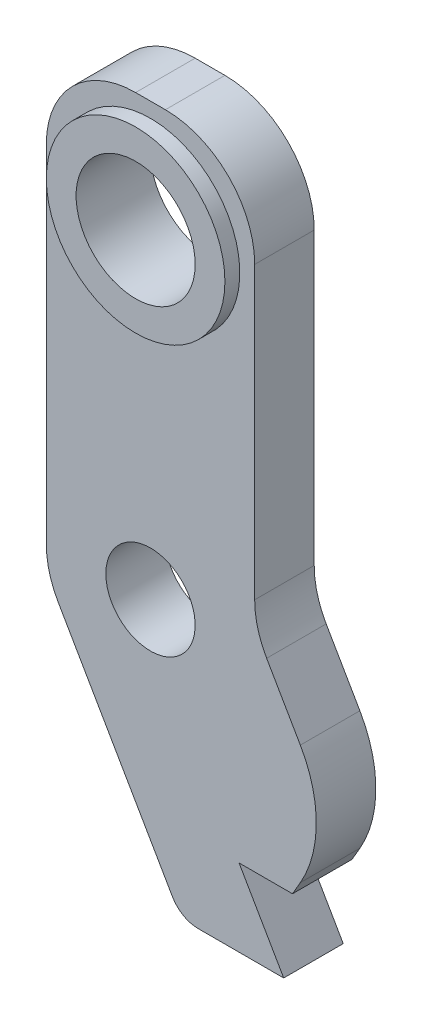
SolidWorks part; units mm, degrees
ref_plane "前视基准面" through (0, 0, 0) normal (0, 0, 1) x (1, 0, 0)
ref_plane "上视基准面" through (0, 0, 0) normal (0, 1, 0) x (1, 0, 0)
ref_plane "右视基准面" through (0, 0, 0) normal (1, 0, 0) x (0, 0, -1)
sketch "草图1" plane through (0, 0, -37.2525) normal (0, 0, 1) x (1, 0, 0)
  line L0 (-5.7048, 8.9994) -> (-14.0004, 8.9994) construction
  line L1 (-14.0004, 8.9994) -> (-11.3913, 4.4807) construction
  line L2 (-14.0004, 8.9994) -> (-14.0004, 23.4994) construction
  line L3 (-10.5004, 9.9373) -> (-10.5004, 23.4994)
  line L5 (-10.5004, 23.4994) -> (-17.5004, 23.4994)
  line L6 (-17.5004, 8.0615) -> (-12.976, 0.2258)
  line L7 (-17.5004, 23.4994) -> (-17.5004, 8.0615)
  line L11 (-12.976, 0.2258) -> (-9.5249, 0.2258)
  line L13 (-9.5249, 0.2258) -> (-11.025, 2.8238)
  line L14 (-11.025, 2.8238) -> (-9.2297, 2.8239)
  line L18 (-10.5004, 9.9373) -> (-7.8115, 5.2805)
  line L19 (-7.8115, 5.2805) -> (-9.2297, 2.8239)
  circle A0 centre (-14.0004, 19.9994) radius 2
  circle A1 centre (-14.0004, 8.9994) radius 1.5
  dimension "D7" = 120
  dimension "D4" = 7
  dimension "D9" = 3.5
  dimension "D10" = 3.5
  dimension "D3" = 3
  dimension "D8" = 11
  dimension "D1" = 4
  dimension "D2" = 59.997
  dimension "D5" = 7
  dimension "D6" = 3
extrude "凸台-拉伸1" add sketch "草图1" along normal up to surface (2 mm away)
fillet "圆角1" radius 3 4 edges at (-10.4993, 23.4998, -36.2525) (-17.4993, 23.5002, -36.2525) (-10.5, 9.9377, -36.2525) (-17.5, 8.0623, -36.2525)
fillet "圆角2" radius 4 1 edges at (-7.8113, 5.2809, -36.2525)
fillet "圆角3" radius 1 1 edges at (-12.976, 0.2264, -36.2525)
sketch "草图2" plane through (-0.251, -0.0681, -35.2525) normal (0, 0, 1) x (1, 0, 0)
  circle A0 centre (-13.7485, 20.0681) radius 3
  circle A1 centre (-13.7485, 20.0681) radius 2 construction
  circle A3 centre (-13.7485, 20.0681) radius 2
  dimension "D1" = 6
extrude "凸台-拉伸2" add sketch "草图2" along normal blind 0.5
